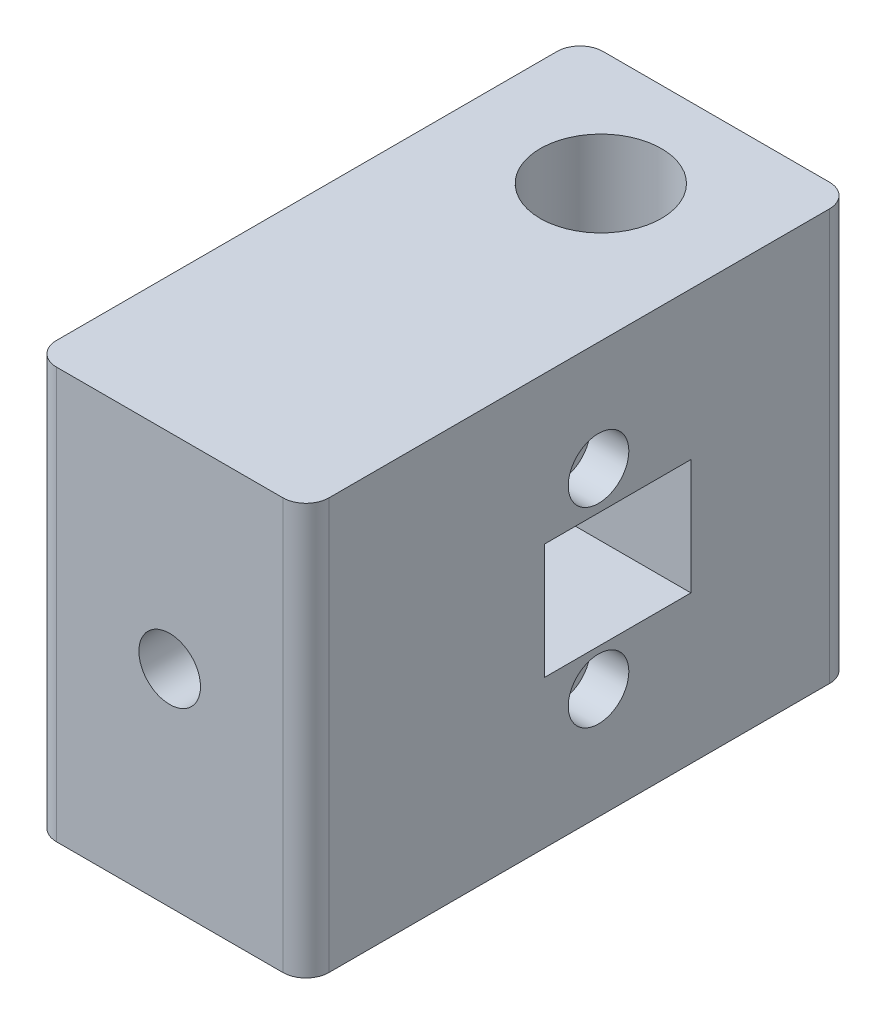
SolidWorks part; units mm, degrees
ref_plane "Front Plane" through (0, 0, 0) normal (0, 0, 1) x (1, 0, 0)
ref_plane "Top Plane" through (0, 0, 0) normal (0, 1, 0) x (1, 0, 0)
ref_plane "Right Plane" through (0, 0, 0) normal (1, 0, 0) x (0, 0, -1)
sketch "Sketch1" plane through (0, 0, 0) normal (0, 0, 1) x (1, 0, 0)
  line L1 (0, 0) -> (44.958, 0)
  line L2 (0, 0) -> (0, 67.818)
  line L3 (0, 67.818) -> (44.958, 67.818)
  line L4 (44.958, 0) -> (44.958, 67.818)
  dimension "D1" = 44.958
  dimension "D2" = 67.818
extrude "Boss-Extrude1" add sketch "Sketch1" along normal blind 90.17
sketch "Sketch2" plane through (44.958, 0, 0) normal (1, 0, 0) x (0, 0, -1)
  line L0 (-90.17, 0) -> (-90.17, 67.818) construction
  line L3 (-90.17, 0) -> (0, 0) construction
  circle A0 centre (-41.91, 49.788) radius 5
  circle A1 centre (-41.91, 18.288) radius 5
  dimension "D2" = 10
  dimension "D4" = 10
  dimension "D1" = 48.26
  dimension "D3" = 31.5
  dimension "D5" = 18.288
extrude "Cut-Extrude1" cut sketch "Sketch2" against normal blind 6.35
sketch "Sketch3" plane through (0, 67.818, 0) normal (0, 1, 0) x (1, 0, 0)
  line L0 (44.958, 0) -> (0, 0) construction
  line L1 (0, -90.17) -> (0, 0) construction
  circle A0 centre (22.479, -19.05) radius 4.064
  dimension "D1" = 8.128
  dimension "D2" = 19.05
  dimension "D3" = 22.479
extrude "Cut-Extrude2" cut sketch "Sketch3" against normal through all
sketch "Sketch4" plane through (0, 67.818, 0) normal (0, 1, 0) x (1, 0, 0)
  circle A0 centre (22.479, -19.05) radius 9.9949
  dimension "D1" = 19.9898
extrude "Cut-Extrude3" cut sketch "Sketch4" against normal blind 15.24
sketch "Sketch5" plane through (0, 0, 90.17) normal (0, 0, 1) x (1, 0, 0)
  line L0 (0, 0) -> (44.958, 0) construction
  line L1 (0, 67.818) -> (0, 0) construction
  circle A0 centre (22.479, 34.036) radius 5.08
  dimension "D3" = 10.16
  dimension "D1" = 34.036
  dimension "D2" = 22.479
extrude "Cut-Extrude4" cut sketch "Sketch5" against normal blind 50.8
sketch "Sketch6" plane through (44.958, 0, 0) normal (1, 0, 0) x (0, 0, -1)
  line L0 (-90.17, 0) -> (0, 0) construction
  line L1 (-50.8, 43.434) -> (-26.67, 43.434)
  line L2 (-50.8, 43.434) -> (-50.8, 24.384)
  line L3 (-50.8, 24.384) -> (-26.67, 24.384)
  line L4 (-26.67, 43.434) -> (-26.67, 24.384)
  line L5 (-90.17, 0) -> (-90.17, 67.818) construction
  dimension "D1" = 24.13
  dimension "D2" = 19.05
  dimension "D3" = 24.384
  dimension "D4" = 63.5
extrude "Cut-Extrude5" cut sketch "Sketch6" against normal blind 34.29
fillet "Fillet1" radius 3.81 4 edges at (0, 33.909, 0) (44.958, 33.909, 0) (0, 33.909, 90.17) (44.958, 33.909, 90.17)
